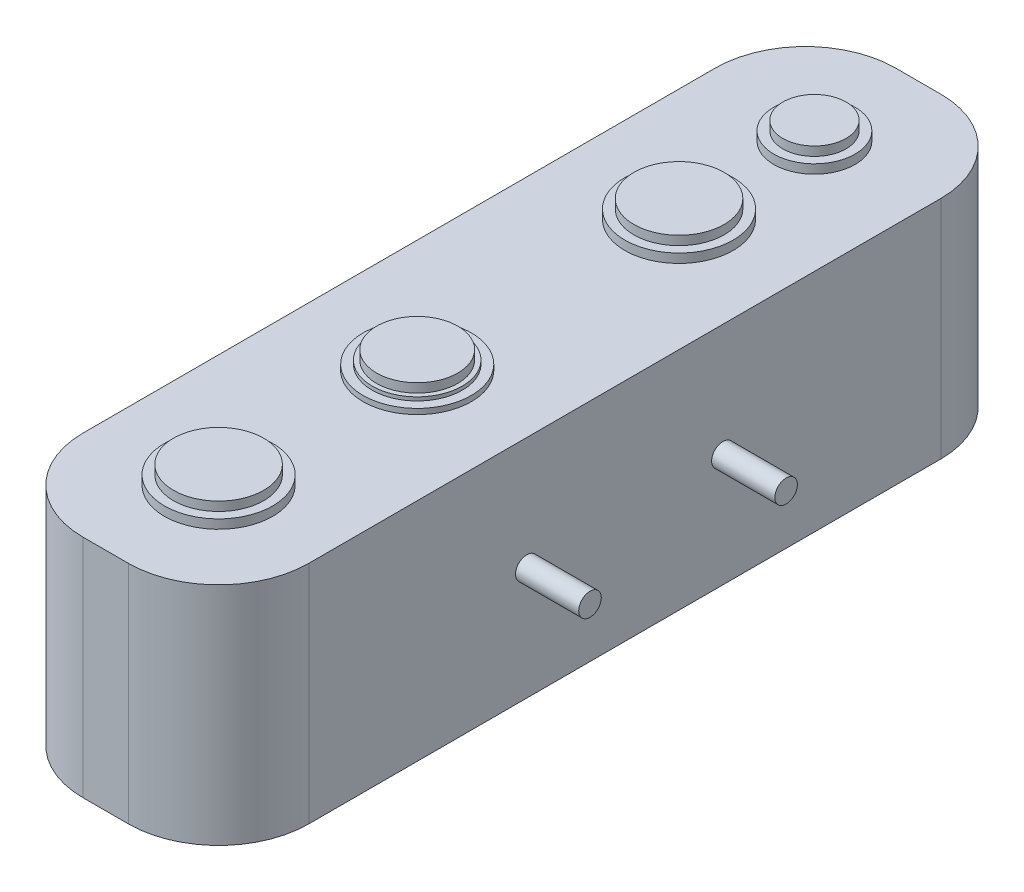
SolidWorks part; units mm, degrees
ref_plane "Front Plane" through (0, 0, 0) normal (0, 0, 1) x (1, 0, 0)
ref_plane "Top Plane" through (0, 0, 0) normal (0, 1, 0) x (1, 0, 0)
ref_plane "Right Plane" through (0, 0, 0) normal (1, 0, 0) x (0, 0, -1)
sketch "Sketch1" plane through (0, 0, 0) normal (0, 1, 0) x (1, 0, 0)
  line L1 (-12.5, 45) -> (12.5, 45)
  line L2 (-12.5, 45) -> (-12.5, -45)
  line L3 (-12.5, -45) -> (12.5, -45)
  line L4 (12.5, 45) -> (12.5, -45)
  line L5 (-12.5, 45) -> (12.5, -45) construction
  line L6 (-12.5, -45) -> (12.5, 45) construction
  point P0 (0, 0)
  dimension "D1" = 90
  dimension "D2" = 25
extrude "Boss-Extrude1" add sketch "Sketch1" along normal blind 25
sketch "Sketch2" plane through (0, 25, 0) normal (0, 1, 0) x (1, 0, 0)
  line L0 (0, 45) -> (0, -45)
  line L1 (12.5, 45) -> (-12.5, 45) construction
  line L2 (-12.5, -45) -> (12.5, -45) construction
  line L3 (0, -45) -> (0, -32.5)
  line L4 (0, -32.5) -> (0, 18.5)
  line L5 (0, 18.5) -> (0, 33.5)
  line L6 (0, 18.5) -> (0, -10.5)
  circle A0 centre (0, -32.5) radius 5
  circle A1 centre (0, 18.5) radius 5
  circle A2 centre (0, 33.5) radius 3.5
  circle A3 centre (0, -10.5) radius 4.5
  circle A4 centre (0, -32.5) radius 6
  circle A5 centre (0, 18.5) radius 6
  circle A6 centre (0, 33.5) radius 4.5
  circle A7 centre (0, -10.5) radius 5
  circle A8 centre (0, -10.5) radius 6
  dimension "D2" = 10
  dimension "D4" = 10
  dimension "D6" = 7
  dimension "D8" = 9
  dimension "D9" = 12
  dimension "D10" = 12
  dimension "D11" = 9
  dimension "D12" = 10
  dimension "D13" = 12
  dimension "D1" = 12.5
  dimension "D3" = 51
  dimension "D5" = 15
  dimension "D7" = 29
extrude "Boss-Extrude2" add sketch "Sketch2" along normal blind 2 contours A0 | A3 | A1 | A2
extrude "Boss-Extrude3" add sketch "Sketch2<3>" along normal blind 1 contours A4 | A5 | A7 | A6
sketch "Sketch2<3>" plane through (0, 25, 0) normal (0, 1, 0) x (1, 0, 0) same geometry as "Sketch2"
extrude "Boss-Extrude4" add sketch "Sketch2<4>" along normal blind 0.6 contours A8
sketch "Sketch2<4>" plane through (0, 25, 0) normal (0, 1, 0) x (1, 0, 0) same geometry as "Sketch2"
fillet "Fillet1" radius 10 4 edges at (-12.5, 12.5, 45) (12.5, 12.5, 45) (12.5, 12.5, -45) (-12.5, 12.5, -45)
sketch "Sketch3" plane through (12.5, 0, 0) normal (1, 0, 0) x (0, 0, -1)
  line L0 (-35, 12.5) -> (35, 12.5)
  line L1 (-35, 25) -> (-35, 0) construction
  line L2 (35, 0) -> (35, 25) construction
  line L3 (0, 12.5) -> (10.86, 12.5)
  line L4 (0, 12.5) -> (-10.86, 12.5)
  circle A0 centre (-10.86, 12.5) radius 1.25
  circle A1 centre (10.86, 12.5) radius 1.25
  dimension "D3" = 2.5
  dimension "D4" = 2.5
  dimension "D1" = 10.86
  dimension "D2" = 10.86
extrude "Boss-Extrude5" add sketch "Sketch3" along normal blind 7 contours A1 | A0
